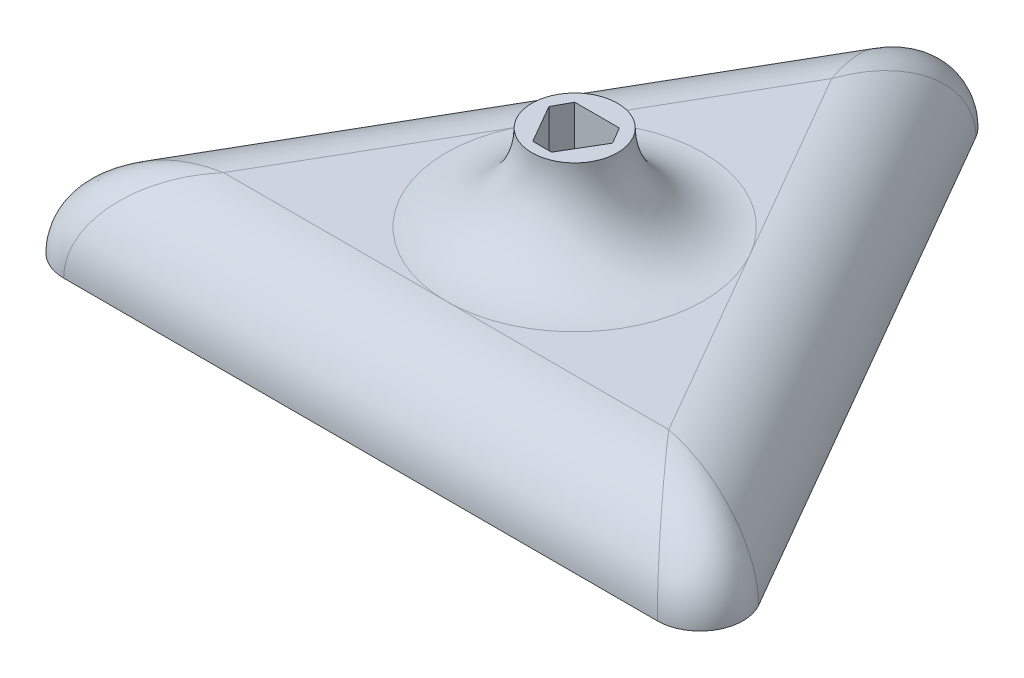
SolidWorks part; units mm, degrees
ref_plane "Front Plane" through (0, 0, 0) normal (0, 0, 1) x (1, 0, 0)
ref_plane "Top Plane" through (0, 0, 0) normal (0, 1, 0) x (1, 0, 0)
ref_plane "Right Plane" through (0, 0, 0) normal (1, 0, 0) x (0, 0, -1)
sketch "Sketch1" plane through (0, 0, 0) normal (0, 1, 0) x (1, 0, 0)
  line L1 (0, 50) -> (-43.3013, -25)
  line L2 (-43.3013, -25) -> (43.3013, -25)
  line L3 (43.3013, -25) -> (0, 50)
  circle A0 centre (0, 0) radius 50 construction
  dimension "D1" = 100
extrude "Boss-Extrude1" add sketch "Sketch1" along normal blind 10
fillet "Fillet1" radius 5 3 edges at (0, 5, -50) (43.3013, 5, 25) (-43.3013, 5, 25)
sketch "Sketch2" plane through (0, 10, 0) normal (0, 1, 0) x (1, 0, 0)
  circle A0 centre (0, 0) radius 3.8
sketch "Sketch3" plane through (0, 10, 0) normal (0, 1, 0) x (1, 0, 0)
  line L0 (0, 3.8) -> (0, -3.8)
sketch "Sketch5" plane through (0, 10, 0) normal (0, 1, 0) x (1, 0, 0)
  line L0 (-3.6756, 0.6709) -> (-2.6043, 2.6062)
  line L1 (-2.6043, 2.6062) -> (2.6043, 2.6062)
  line L2 (2.6043, 2.6062) -> (3.7403, 0.6709)
  line L3 (3.7403, 0.6709) -> (1.0943, -3.8)
  line L4 (1.0943, -3.8) -> (-1.0943, -3.8)
  line L5 (-1.0943, -3.8) -> (-3.6756, 0.6709)
  circle A0 centre (0, 0) radius 5
extrude "Boss-Extrude2" add sketch "Sketch5" along normal blind 10
fillet "Fillet2" radius 10 7 edges at (0, 10, 5) (38.9711, 10, 22.5) (0, 10, 25) (-38.9711, 10, 22.5) (-21.6506, 10, -12.5) (0, 10, -45) (21.6506, 10, -12.5)
